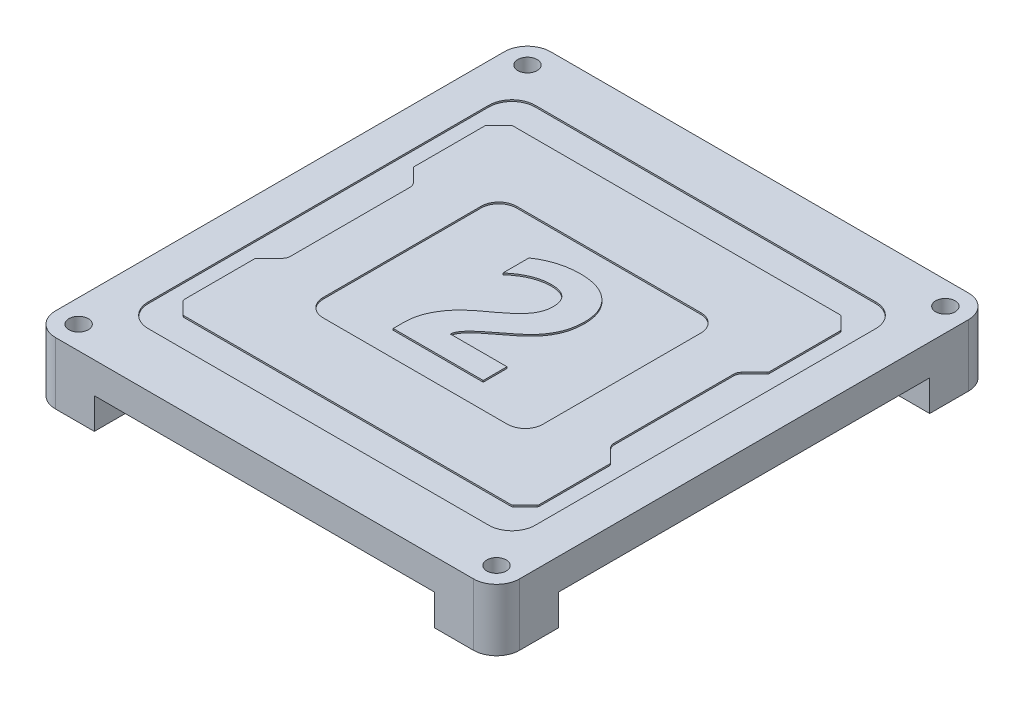
SolidWorks part; units mm, degrees
ref_plane "前视基准面" through (0, 0, 0) normal (0, 0, 1) x (1, 0, 0)
ref_plane "上视基准面" through (0, 0, 0) normal (0, 1, 0) x (1, 0, 0)
ref_plane "右视基准面" through (0, 0, 0) normal (1, 0, 0) x (0, 0, -1)
other "Configuration Table"
sketch "草图1" plane through (0, 0, 0) normal (0, 1, 0) x (1, 0, 0)
  line L8 (-27.0001, -31.9874) -> (27.0001, -31.9874)
  line L9 (29.9874, -29.0001) -> (29.9874, 29.0001)
  line L10 (27.0001, 31.9874) -> (-27.0001, 31.9874)
  line L11 (-29.9874, 29.0001) -> (-29.9874, -29.0001)
  line L12 (-27.0001, -31.9874) -> (27.0001, -31.9874)
  line L13 (29.9874, -29.0001) -> (29.9874, 29.0001)
  line L14 (27.0001, 31.9874) -> (-27.0001, 31.9874)
  line L15 (-29.9874, 29.0001) -> (-29.9874, -29.0001)
  arc A4 (27.0001, -31.9874) -> (29.9874, -29.0001) centre (27.0001, -29.0001) ccw
  arc A5 (29.9874, 29.0001) -> (27.0001, 31.9874) centre (27.0001, 29.0001) ccw
  arc A6 (-27.0001, 31.9874) -> (-29.9874, 29.0001) centre (-27.0001, 29.0001) ccw
  arc A7 (-29.9874, -29.0001) -> (-27.0001, -31.9874) centre (-27.0001, -29.0001) ccw
  arc A8 (27.0001, -31.9874) -> (29.9874, -29.0001) centre (27.0001, -29.0001) ccw
  arc A9 (29.9874, 29.0001) -> (27.0001, 31.9874) centre (27.0001, 29.0001) ccw
  arc A10 (-27.0001, 31.9874) -> (-29.9874, 29.0001) centre (-27.0001, 29.0001) ccw
  arc A11 (-29.9874, -29.0001) -> (-27.0001, -31.9874) centre (-27.0001, -29.0001) ccw
  dimension "D1" = 0
extrude "凸台-拉伸1" add sketch "草图1" along normal blind 4
sketch "草图2" plane through (0, 0, 0) normal (0, -1, 0) x (1, 0, 0)
  line L4 (-21.9874, 23.9874) -> (-21.9874, 31.9874)
  line L5 (-21.9874, 31.9874) -> (-27.0001, 31.9874)
  line L6 (-29.9874, 29.0001) -> (-29.9874, 23.9874)
  line L7 (-29.9874, 23.9874) -> (-21.9874, 23.9874)
  line L8 (-21.9874, 23.9874) -> (-21.9874, 31.9874)
  line L9 (-21.9874, 31.9874) -> (-27.0001, 31.9874)
  line L10 (-29.9874, 29.0001) -> (-29.9874, 23.9874)
  line L11 (-29.9874, 23.9874) -> (-21.9874, 23.9874)
  line L12 (21.9874, -23.9874) -> (21.9874, -31.9874)
  line L13 (21.9874, -31.9874) -> (27.0001, -31.9874)
  line L14 (29.9874, -29.0001) -> (29.9874, -23.9874)
  line L15 (29.9874, -23.9874) -> (21.9874, -23.9874)
  line L16 (21.9874, -23.9874) -> (21.9874, -31.9874)
  line L17 (21.9874, -31.9874) -> (27.0001, -31.9874)
  line L18 (29.9874, -29.0001) -> (29.9874, -23.9874)
  line L19 (29.9874, -23.9874) -> (21.9874, -23.9874)
  line L20 (21.9874, 23.9874) -> (29.9874, 23.9874)
  line L21 (29.9874, 23.9874) -> (29.9874, 29.0001)
  line L22 (27.0001, 31.9874) -> (21.9874, 31.9874)
  line L23 (21.9874, 31.9874) -> (21.9874, 23.9874)
  line L24 (21.9874, 23.9874) -> (29.9874, 23.9874)
  line L25 (29.9874, 23.9874) -> (29.9874, 29.0001)
  line L26 (27.0001, 31.9874) -> (21.9874, 31.9874)
  line L27 (21.9874, 31.9874) -> (21.9874, 23.9874)
  line L28 (-29.9874, -23.9874) -> (-29.9874, -29.0001)
  line L29 (-21.9874, -23.9874) -> (-29.9874, -23.9874)
  line L30 (-21.9874, -31.9874) -> (-21.9874, -23.9874)
  line L31 (-27.0001, -31.9874) -> (-21.9874, -31.9874)
  line L32 (-29.9874, -23.9874) -> (-29.9874, -29.0001)
  line L33 (-21.9874, -23.9874) -> (-29.9874, -23.9874)
  line L34 (-21.9874, -31.9874) -> (-21.9874, -23.9874)
  line L35 (-27.0001, -31.9874) -> (-21.9874, -31.9874)
  arc A1 (-27.0001, 31.9874) -> (-29.9874, 29.0001) centre (-27.0001, 29.0001) ccw
  arc A2 (-27.0001, 31.9874) -> (-29.9874, 29.0001) centre (-27.0001, 29.0001) ccw
  arc A3 (27.0001, -31.9874) -> (29.9874, -29.0001) centre (27.0001, -29.0001) ccw
  arc A4 (27.0001, -31.9874) -> (29.9874, -29.0001) centre (27.0001, -29.0001) ccw
  arc A5 (29.9874, 29.0001) -> (27.0001, 31.9874) centre (27.0001, 29.0001) ccw
  arc A6 (29.9874, 29.0001) -> (27.0001, 31.9874) centre (27.0001, 29.0001) ccw
  arc A7 (-29.9874, -29.0001) -> (-27.0001, -31.9874) centre (-27.0001, -29.0001) ccw
  arc A8 (-29.9874, -29.0001) -> (-27.0001, -31.9874) centre (-27.0001, -29.0001) ccw
  dimension "D1" = 0
  dimension "D2" = 0
  dimension "D3" = 0
  dimension "D4" = 0
extrude "凸台-拉伸2" add sketch "草图2" along normal blind 4
sketch "草图3" plane through (0, -4, 0) normal (0, -1, 0) x (1, 0, 0)
  circle A0 centre (-27.0001, 29.0001) radius 1.25
  circle A1 centre (27.0001, 29.0001) radius 1.25
  circle A2 centre (27.0001, -29.0001) radius 1.25
  circle A3 centre (-27.0001, -29.0001) radius 1.25
  dimension "D1" = 2.5
  dimension "D2" = 2.5
  dimension "D3" = 2.5
  dimension "D4" = 2.5
extrude "切除-拉伸1" cut sketch "草图3" against normal blind 15
sketch "草图4" plane through (0, 4, 0) normal (0, 1, 0) x (1, 0, 0)
  line L1 (-22, -25) -> (22, -25)
  line L2 (-25, -22) -> (-25, 22)
  line L3 (-22, 25) -> (22, 25)
  line L4 (25, -22) -> (25, 22)
  line L5 (0, 25) -> (0, -25) construction
  line L6 (-25, 0) -> (25, 0) construction
  arc A0 (-22, -25) -> (-25, -22) centre (-22, -22) cw
  arc A1 (25, 22) -> (22, 25) centre (22, 22) ccw
  arc A2 (25, -22) -> (22, -25) centre (22, -22) cw
  arc A3 (-25, 22) -> (-22, 25) centre (-22, 22) cw
  point P0 (0, 0)
  point P6 (-25, -25)
  point P16 (-25, 25)
  dimension "D2" = 3
  dimension "D1" = 50
extrude "切除-拉伸2" cut sketch "草图4" against normal blind 0.2
sketch "草图9" plane through (0, 3.8, 0) normal (0, 1, 0) x (1, 0, 0)
  line L4 (-20.91, 7.7375) -> (-20.91, -7.7375)
  line L5 (-21.2088, -8.4588) -> (-22.8504, -10.1004)
  line L6 (-22.95, -10.3408) -> (-22.95, -19.4092)
  line L7 (-22.8504, -19.6496) -> (-21.3496, -21.1504)
  line L8 (-21.1092, -21.25) -> (21.1092, -21.25)
  line L9 (21.3496, -21.1504) -> (22.8504, -19.6496)
  line L10 (22.95, -19.4092) -> (22.95, -10.3408)
  line L11 (22.8504, -10.1004) -> (21.2088, -8.4588)
  line L12 (20.91, -7.7375) -> (20.91, 7.7375)
  line L13 (21.2088, 8.4588) -> (22.8504, 10.1004)
  line L14 (22.95, 10.3408) -> (22.95, 19.4092)
  line L15 (22.8504, 19.6496) -> (21.3496, 21.1504)
  line L16 (21.1092, 21.25) -> (-21.1092, 21.25)
  line L17 (-21.3496, 21.1504) -> (-22.8504, 19.6496)
  line L18 (-22.95, 19.4092) -> (-22.95, 10.3408)
  line L19 (-22.8504, 10.1004) -> (-21.2088, 8.4588)
  line L20 (-11.9, -12.495) -> (11.9, -12.495)
  line L21 (14.195, -10.2) -> (14.195, 10.2)
  line L22 (-14.195, 10.2) -> (-14.195, -10.2)
  line L23 (11.9, 12.495) -> (-11.9, 12.495)
  line L24 (-11.9, 0) -> (11.9, 0) construction
  line L25 (0, 11.305) -> (0, -11.305) construction
  line L27 (-10.9, -10.2) -> (10.9, -10.2)
  line L28 (-11.9, -9.2) -> (-11.9, 9.2)
  line L29 (-10.9, 10.2) -> (10.9, 10.2)
  line L30 (11.9, -9.2) -> (11.9, 9.2)
  line L31 (0, 10.2) -> (0, -10.2) construction
  line L32 (-11.9, 0) -> (11.9, 0) construction
  arc A4 (-20.91, 7.7375) -> (-21.2088, 8.4588) centre (-21.93, 7.7375) ccw
  arc A5 (-21.2088, -8.4588) -> (-20.91, -7.7375) centre (-21.93, -7.7375) ccw
  arc A6 (-22.8504, -10.1004) -> (-22.95, -10.3408) centre (-22.61, -10.3408) ccw
  arc A7 (-22.95, -19.4092) -> (-22.8504, -19.6496) centre (-22.61, -19.4092) ccw
  arc A8 (-21.3496, -21.1504) -> (-21.1092, -21.25) centre (-21.1092, -20.91) ccw
  arc A9 (21.1092, -21.25) -> (21.3496, -21.1504) centre (21.1092, -20.91) ccw
  arc A10 (22.8504, -19.6496) -> (22.95, -19.4092) centre (22.61, -19.4092) ccw
  arc A11 (22.95, -10.3408) -> (22.8504, -10.1004) centre (22.61, -10.3408) ccw
  arc A12 (20.91, -7.7375) -> (21.2088, -8.4588) centre (21.93, -7.7375) ccw
  arc A13 (21.2088, 8.4588) -> (20.91, 7.7375) centre (21.93, 7.7375) ccw
  arc A14 (22.8504, 10.1004) -> (22.95, 10.3408) centre (22.61, 10.3408) ccw
  arc A15 (22.95, 19.4092) -> (22.8504, 19.6496) centre (22.61, 19.4092) ccw
  arc A16 (21.3496, 21.1504) -> (21.1092, 21.25) centre (21.1092, 20.91) ccw
  arc A17 (-21.1092, 21.25) -> (-21.3496, 21.1504) centre (-21.1092, 20.91) ccw
  arc A18 (-22.8504, 19.6496) -> (-22.95, 19.4092) centre (-22.61, 19.4092) ccw
  arc A19 (-22.95, 10.3408) -> (-22.8504, 10.1004) centre (-22.61, 10.3408) ccw
  arc A20 (-17.612, -17.765) -> (-14.688, -17.765) centre (-16.15, -17.765) ccw
  arc A21 (-14.688, -17.765) -> (-17.612, -17.765) centre (-16.15, -17.765) ccw
  arc A22 (14.688, 17.765) -> (17.612, 17.765) centre (16.15, 17.765) ccw
  arc A23 (17.612, 17.765) -> (14.688, 17.765) centre (16.15, 17.765) ccw
  arc A24 (-17.612, 17.765) -> (-14.688, 17.765) centre (-16.15, 17.765) ccw
  arc A25 (-14.688, 17.765) -> (-17.612, 17.765) centre (-16.15, 17.765) ccw
  arc A26 (17.612, -17.765) -> (14.688, -17.765) centre (16.15, -17.765) ccw
  arc A27 (14.688, -17.765) -> (17.612, -17.765) centre (16.15, -17.765) ccw
  arc A28 (-14.195, -10.2) -> (-11.9, -12.495) centre (-11.9, -10.2) ccw
  arc A29 (11.9, -12.495) -> (14.195, -10.2) centre (11.9, -10.2) ccw
  arc A30 (14.195, 10.2) -> (11.9, 12.495) centre (11.9, 10.2) ccw
  arc A31 (-11.9, 12.495) -> (-14.195, 10.2) centre (-11.9, 10.2) ccw
  arc A32 (-11.9, 9.2) -> (-10.9, 10.2) centre (-10.9, 9.2) cw
  arc A33 (11.9, -9.2) -> (10.9, -10.2) centre (10.9, -9.2) cw
  arc A34 (-10.9, -10.2) -> (-11.9, -9.2) centre (-10.9, -9.2) cw
  arc A35 (11.9, 9.2) -> (10.9, 10.2) centre (10.9, 9.2) ccw
  point P84 (0, 0)
  dimension "D1" = 1
extrude "凸台-拉伸5" add sketch "草图9" along normal blind 0.2 contours L18 A19 L19 A4 L4 A5 L5 A6 L6 A7 L7 A8 L8 A9 L9 A10 L10 A11 L11 A12 L12 A13 L13 A14 L14 A15 L15 A16 L16 A17 L17 A18 A31 L23 A30 L21 A29 L20 A28 L22 A27 A26 A25 A24 A23 A22 region at (-20.4097, 3.8, -8.3672)
sketch "草图12" plane through (0, 3.8, 0) normal (0, 1, 0) x (1, 0, 0)
  text T0 "2" font "微软雅黑" height 18
extrude "凸台-拉伸6" add sketch "草图12" along normal blind 0.2
sketch "草图13" plane through (0, 3.8, 0) normal (0, 1, 0) x (1, 0, 0)
  circle A0 centre (-16.15, 17.765) radius 2.2806
  circle A1 centre (16.15, 17.765) radius 2.9348
  circle A2 centre (16.15, -17.765) radius 2.6308
  circle A3 centre (-16.15, -17.765) radius 2.8482
extrude "凸台-拉伸7" add sketch "草图13" along normal blind 0.2
sketch "草图16" plane through (0, 4, 0) normal (0, 1, 0) x (1, 0, 0)
  circle A0 centre (-17.6985, 17.3288) radius 1.5
  circle A1 centre (-17.6985, -16.5385) radius 1.5
  circle A2 centre (18.1136, -16.5385) radius 1.5
  dimension "D1" = 3
  dimension "D2" = 3
  dimension "D3" = 3
extrude "切除-拉伸8" [suppressed] cut sketch "草图16" against normal blind 0.2
